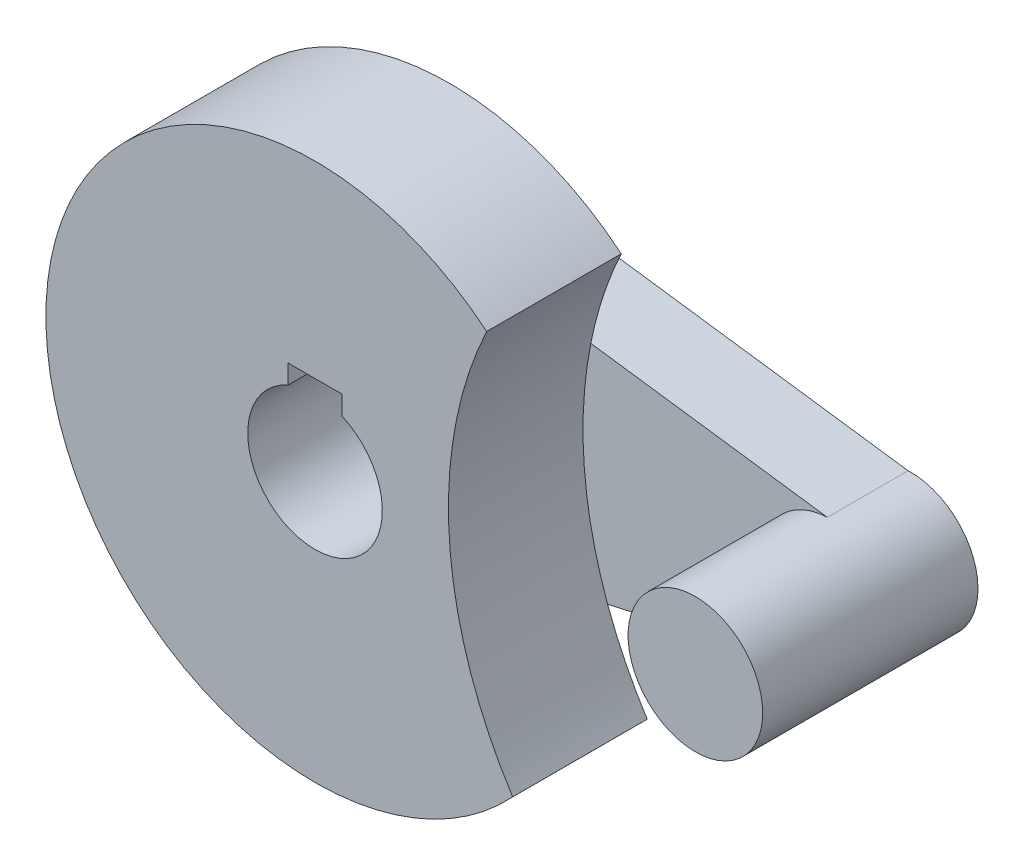
SolidWorks part; units mm, degrees
ref_plane "前视基准面" through (0, 0, 0) normal (0, 0, 1) x (1, 0, 0)
ref_plane "上视基准面" through (0, 0, 0) normal (0, 1, 0) x (1, 0, 0)
ref_plane "右视基准面" through (0, 0, 0) normal (1, 0, 0) x (0, 0, -1)
other "Configuration Table"
sketch "草图1" plane through (0, 0, 0) normal (0, 0, 1) x (1, 0, 0)
  circle A0 centre (0, 0) radius 10
  circle A1 centre (0, 0) radius 2.5
  dimension "D1" = 5
  dimension "D2" = 20
extrude "凸台-拉伸1" add sketch "草图1" along normal blind 5
sketch "草图2" plane through (0, 0, 0) normal (0, 0, -1) x (-1, 0, 0)
  circle A0 centre (-19.9558, 1.3288) radius 15
extrude "切除-拉伸1" cut sketch "草图2" against normal blind 5
sketch "草图3" plane through (0, 0, 0) normal (0, 0, -1) x (-1, 0, 0)
  line L0 (-14.6846, -13.578) -> (0, 0) construction
  line L1 (-14.6846, -13.578) -> (-14.0004, 3.8975) construction
  line L2 (0, 0) -> (-14.1313, 0.5533) construction
  line L3 (-14.0335, 3.0513) -> (0.1636, 4.9973)
  line L4 (-14.6692, -1.8882) -> (-1.0757, -4.8829)
  circle A0 centre (0, 0) radius 2.5
  arc A1 (-1.0757, -4.8829) -> (0.1636, 4.9973) centre (0, 0) ccw
  arc A2 (-14.0335, 3.0513) -> (-14.6692, -1.8882) centre (-14.1313, 0.5533) ccw
  dimension "D1" = 10
  dimension "D2" = 5
extrude "凸台-拉伸2" add sketch "草图3" along normal blind 3
sketch "草图4" plane through (0, 0, 0) normal (0, 0, 1) x (1, 0, 0)
  circle A0 centre (14.1313, 0.5533) radius 2.5
  dimension "D1" = 5
extrude "凸台-拉伸3" add sketch "草图4" along normal blind 5
sketch "草图5" plane through (0, 0, 5) normal (0, 0, 1) x (1, 0, 0)
  line L1 (-1, 3) -> (1, 3)
  line L2 (-1, 3) -> (-1, 2)
  line L3 (-1, 2) -> (1, 2)
  line L4 (1, 3) -> (1, 2)
  line L5 (-1, 3) -> (1, 2) construction
  line L6 (-1, 2) -> (1, 3) construction
  circle A0 centre (0, 0) radius 2.5 construction
  point P0 (0, 2.5)
  dimension "D1" = 2
  dimension "D2" = 1
extrude "切除-拉伸2" cut sketch "草图5" against normal through all
